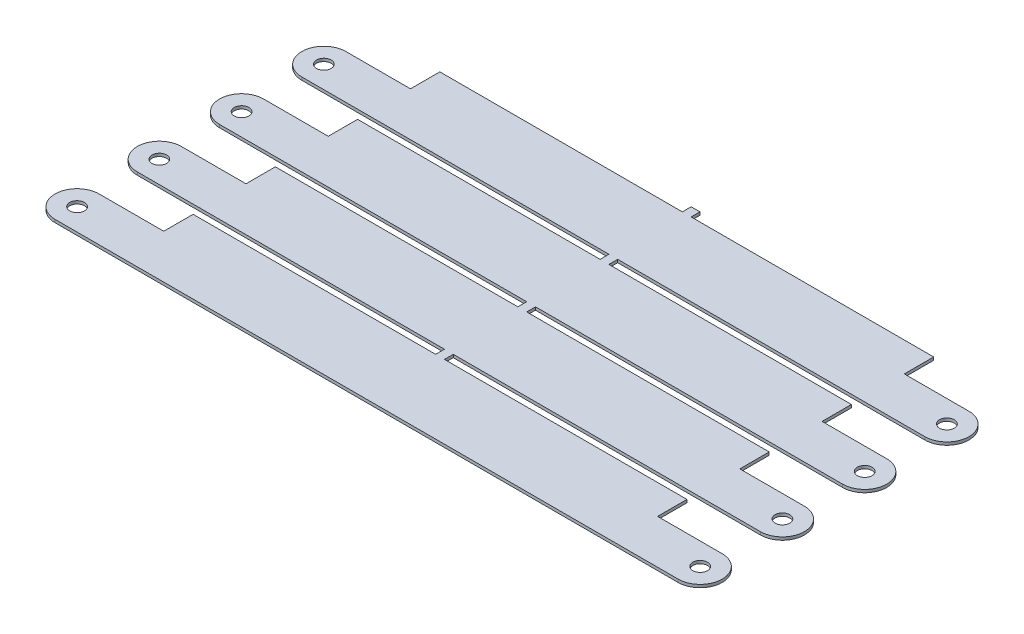
SolidWorks part; units mm, degrees
ref_plane "Front Plane" through (0, 0, 0) normal (0, 0, 1) x (1, 0, 0)
ref_plane "Top Plane" through (0, 0, 0) normal (0, 1, 0) x (1, 0, 0)
ref_plane "Right Plane" through (0, 0, 0) normal (1, 0, 0) x (0, 0, -1)
sketch "Sketch1" plane through (0, 0, 0) normal (0, 1, 0) x (1, 0, 0)
  line L0 (0, 0) -> (212.13, 0) construction
  line L1 (0, 7.5) -> (22, 7.5)
  line L2 (0, -7.5) -> (212.13, -7.5)
  line L3 (0, -7.5) -> (0, 7.5) construction
  line L4 (0, 7.5) -> (212.13, 7.5) construction
  line L5 (212.13, -7.5) -> (212.13, 7.5) construction
  line L6 (0, -7.5) -> (212.13, 7.5) construction
  line L7 (0, 7.5) -> (212.13, -7.5) construction
  line L8 (22, 7.5) -> (22, 17.5)
  line L9 (22, 17.5) -> (190.13, 17.5)
  line L10 (190.13, 17.5) -> (190.13, 7.5)
  line L11 (190.13, 7.5) -> (212.13, 7.5)
  line L12 (106.065, 17.5) -> (106.065, 0) construction
  line L13 (104.565, 17.5) -> (104.565, 20.5)
  line L14 (104.565, 20.5) -> (107.565, 20.5)
  line L15 (107.565, 20.5) -> (107.565, 17.5)
  line L16 (106.065, 17.5) -> (106.065, 20.5) construction
  circle A0 centre (0, 0) radius 2.5
  circle A1 centre (212.13, 0) radius 2.5
  arc A2 (0, 7.5) -> (0, -7.5) centre (0, 0) ccw
  arc A3 (212.13, -7.5) -> (212.13, 7.5) centre (212.13, 0) ccw
  point P5 (106.065, 0)
  dimension "D1" = 5
  dimension "D2" = 15
  dimension "D3" = 22
  dimension "D4" = 3
  dimension "D5" = 10
  dimension "D6" = 212.13
  dimension "D7" = 3
extrude "Boss-Extrude1" add sketch "Sketch1" along normal blind 1 contours L2 A3 L11 L10 L9 L8 L1 A2 A0 A1 | L15 L14 L13 L9 region at (106.065, 0, -4.2027) region at (106.065, 0, -19)
pattern_linear "LPattern1" count 4 spacing 28 along (0, 0, -1) of "Boss-Extrude1"
